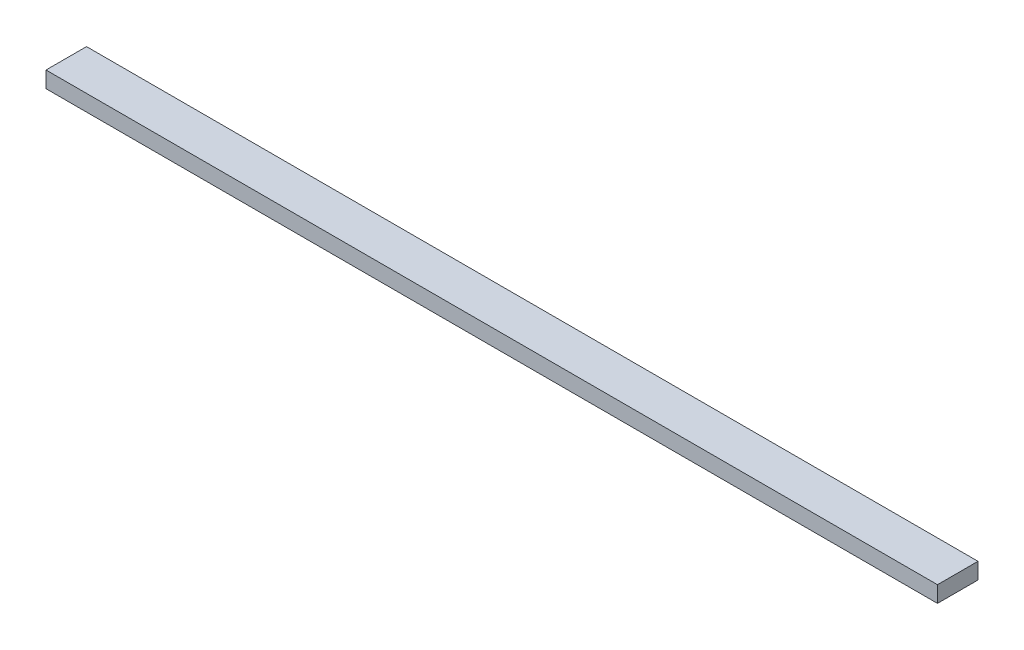
SolidWorks part; units mm, degrees
ref_plane "Front Plane" through (0, 0, 0) normal (0, 0, 1) x (1, 0, 0)
ref_plane "Top Plane" through (0, 0, 0) normal (0, 1, 0) x (1, 0, 0)
ref_plane "Right Plane" through (0, 0, 0) normal (1, 0, 0) x (0, 0, -1)
sketch "Sketch1" plane through (0, 0, 0) normal (0, 1, 0) x (1, 0, 0)
  line L1 (-139.7, 6.35) -> (139.7, 6.35)
  line L2 (-139.7, 6.35) -> (-139.7, -6.35)
  line L3 (-139.7, -6.35) -> (139.7, -6.35)
  line L4 (139.7, 6.35) -> (139.7, -6.35)
  line L5 (-139.7, 6.35) -> (139.7, -6.35) construction
  line L6 (-139.7, -6.35) -> (139.7, 6.35) construction
  point P0 (0, 0)
  dimension "D1" = 12.7
  dimension "D2" = 279.4
extrude "Boss-Extrude1" add sketch "Sketch1" along normal blind 5.08
